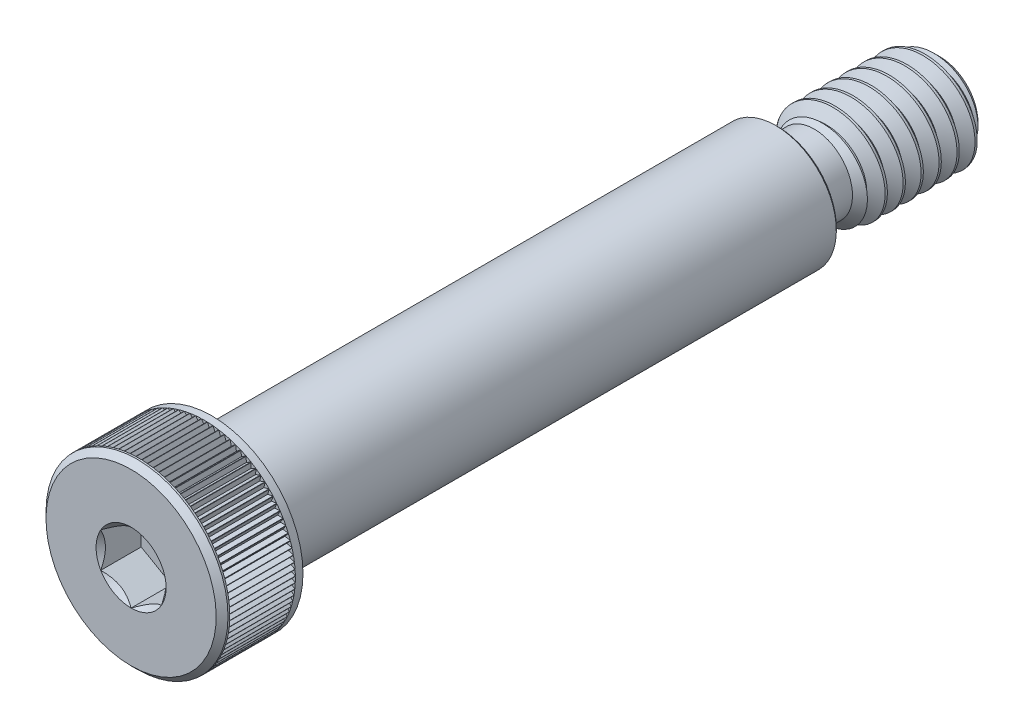
SolidWorks part; units mm, degrees
ref_plane "Front" through (0, 0, 0) normal (0, 0, 1) x (1, 0, 0)
ref_plane "Top" through (0, 0, 0) normal (0, 1, 0) x (1, 0, 0)
ref_plane "Right" through (0, 0, 0) normal (1, 0, 0) x (0, 0, -1)
sketch "Sketch1" plane through (0, 0, 0) normal (1, 0, 0) x (0, 0, -1)
  line L0 (0, 7.1437) -> (6.35, 7.1437)
  line L1 (6.35, 7.1437) -> (6.35, 4.7625)
  line L2 (6.35, 4.7625) -> (50.8, 4.7625)
  line L3 (50.8, 4.7625) -> (50.8, 3.9751)
  line L4 (50.8, 3.9751) -> (63.5, 3.9751)
  line L5 (63.5, 3.9751) -> (63.5, 0)
  line L6 (63.5, 0) -> (0, 0)
  line L7 (0, 0) -> (0, 7.1437)
  line L8 (0, 7.1437) -> (0, -7.1438) construction
  line L9 (63.5, 3.9751) -> (63.5, -3.9751) construction
  line L10 (50.8, 4.7625) -> (50.8, -4.7625) construction
  line L11 (63.5, -3.9751) -> (61.8222, -3.9751) construction
  line L12 (28.575, 0) -> (28.575, 4.7625) construction
  point P8 (61.3833, -3.9751)
  point P12 (50.8, 0)
  point P17 (10.795, 4.7625)
  point P18 (28.575, 0)
  point P19 (28.575, 4.7625)
  point P20 (46.355, 4.7625)
  point P21 (46.355, -4.7625)
  point P22 (10.795, -4.7625)
  dimension "Head Dia" = 14.2875
  dimension "Head Ht" = 6.35
  dimension "Thread Lg" = 12.7
  dimension "Thread Dia" = 7.9502
  dimension "Shoulder Dia" = 9.525
  dimension "Shoulder Lg" = 44.45
  dimension "D1" = 2.1167
  dimension "D2" = 1.6778
  dimension "D3" = 22.225
  dimension "D4" = 4.445
revolve "Revolve1" add sketch "Sketch1" angle 360 mid plane about L6
ref_plane "Plane1" through (0, 0, -63.5) normal (0, 0, 1) x (1, 0, 0)
sketch "Sketch3" plane through (0, 0, -63.5) normal (0, 0, 1) x (1, 0, 0)
  circle A0 centre (0, 0) radius 3.9751
sketch "Sketch5" plane through (0, 0, 0) normal (1, 0, 0) x (0, 0, -1)
  line L0 (50.8, 4.7625) -> (55.372, 4.7625)
  line L1 (55.372, 4.7625) -> (53.6194, 3.0099)
  line L2 (53.6194, 3.0099) -> (51.7652, 3.0099)
  line L3 (50.8, 4.7625) -> (50.8, 3.9751)
  line L5 (50.8, 3.9751) -> (63.5, 3.9751) construction
  line L6 (63.5, 0) -> (53.6194, 0) construction
  line L7 (58.5597, 0) -> (58.5597, -3.9751) construction
  arc A0 (50.8, 3.9751) -> (51.7652, 3.0099) centre (51.7652, 3.9751) ccw
  dimension "D1" = 45
  dimension "CADB" = 2.8194
  dimension "CADA" = 6.0198
revolve "Cut-Revolve1" cut sketch "Sketch5" angle 360 mid plane about L6
chamfer "Chamfer1" distance 0.9938 angle 45 1 edges at (0, 3.9751, -63.5)
chamfer "Chamfer2" distance 0.4643 angle 45 1 edges at (0, 7.1437, 0)
chamfer "Chamfer3" distance 0.2032 angle 45 1 edges at (0, 4.7625, -50.8)
sketch "Sketch10" plane through (0, 0, 0) normal (1, 0, 0) x (0, 0, -1)
  line L0 (0.4643, 0) -> (5.8857, 0) construction
  line L1 (0.4643, -7.1437) -> (0.4643, 7.1437) construction
  line L3 (0.4643, 0) -> (0, 0) construction
  line L4 (5.8857, 0) -> (6.35, 0) construction
  line L5 (6.35, -7.1438) -> (6.35, 7.1437) construction
  point P6 (3.175, 0)
  dimension "D1" = 5.4213
ref_plane "Plane2" through (0, 0, -3.175) normal (0, 0, 1) x (1, 0, 0)
sketch "Sketch11" plane through (0, 0, -3.175) normal (0, 0, 1) x (1, 0, 0)
  line L0 (0, 6.7723) -> (0, 7.1437) construction
  line L1 (0, 6.7723) -> (0.2145, 7.1437)
  line L2 (0, 6.7723) -> (-0.2145, 7.1437)
  line L3 (-0.2145, 7.1437) -> (0.2145, 7.1437)
  line L4 (0, 0) -> (-0.2145, 7.1437) construction
  line L5 (0.2145, 7.1437) -> (0, 0) construction
  circle A1 centre (0, 0) radius 7.1437 construction
  circle A2 centre (0, 0) radius 6.7723 construction
  circle A3 centre (0, 0) radius 6.6794 construction
  point P3 (0, 0.0018)
  point P8 (2.3908, 0.7309)
  dimension "D1" = 0.3715
  dimension "D2" = 3.439
extrude "Cut-Extrude5" cut sketch "Sketch11" against normal mid plane 5.1502
pattern_circular "CirPattern1" count 99 over 360 about axis through (0, 0, -63.5) along (0, 0, -1) of "Cut-Extrude5"
sketch "Sketch8" plane through (0, 0, 0) normal (0, 0, 1) x (1, 0, 0)
  line L1 (2.3813, 1.3748) -> (0, 2.7496)
  line L2 (0, 2.7496) -> (-2.3812, 1.3748)
  line L3 (-2.3812, 1.3748) -> (-2.3812, -1.3748)
  line L4 (-2.3812, -1.3748) -> (0, -2.7496)
  line L5 (0, -2.7496) -> (2.3813, -1.3748)
  line L6 (2.3813, -1.3748) -> (2.3813, 1.3748)
  circle A0 centre (0, 0) radius 2.3812 construction
  dimension "Hex" = 4.7625
extrude "Cut-Extrude2" cut sketch "Sketch8" against normal blind 3.175
sketch "Sketch9" plane through (0, 0, 0) normal (0, 0, 1) x (1, 0, 0)
  circle A0 centre (0, 0) radius 2.7496
extrude "Cut-Extrude4" cut sketch "Sketch9" against normal blind 3.175 draft 45
sketch "Front Sketch" plane through (0, 0, 0) normal (0, 0, 1) x (1, 0, 0)
  line L0 (2.3813, -1.3748) -> (2.3813, 1.3748) construction
  line L1 (-2.3812, 1.3748) -> (-2.3812, -1.3748) construction
  circle A0 centre (0, 0) radius 7.1437 construction
  point P4 (-2.3812, 0)
  point P5 (2.3813, 0)
  point P6 (7.1437, 0)
  point P9 (-7.1437, 0)
ref_plane "Contact Plane 1" through (0, 0, -6.35) normal (0, 0, -1) x (-1, 0, 0)
ref_axis "Center Axis 1" through (0, 0, -63.5) along (0, 0, 1)
curve "Helix/Spiral1" pitch 1.4111 height 14.1111 radius 3.9751 centre (0, 0, -63.5) axis (0, 0, 1) start towards (0, 1, 0)
sketch "Sketch4" plane through (0, 0, 0) normal (1, 0, 0) x (0, 0, -1)
  line L0 (63.4118, 4.1279) -> (64.8229, 4.1279) construction
  line L1 (64.8229, 4.1279) -> (64.1174, 2.9058) construction
  line L3 (64.1174, 2.9058) -> (63.4118, 4.1279) construction
  line L4 (63.4559, 4.0515) -> (64.7788, 4.0515) construction
  line L5 (63.5, 3.9751) -> (64.7347, 3.9751) construction
  line L6 (64.0292, 3.0586) -> (64.2056, 3.0586) construction
  line L7 (64.1174, 3.0586) -> (64.1174, 2.9058) construction
  line L8 (64.1174, 4.1279) -> (64.1174, 3.9751) construction
  line L9 (63.4559, 4.0515) -> (64.7788, 4.0515)
  line L10 (64.7788, 4.0515) -> (64.2056, 3.0586)
  line L11 (64.2056, 3.0586) -> (64.0292, 3.0586)
  line L12 (64.0292, 3.0586) -> (63.4559, 4.0515)
  point P14 (64.1174, 4.0515)
  point P15 (64.1174, 4.1279)
  dimension "D1" = 1.4111
  dimension "D2" = 0.1764
sweep "Cut-Sweep1" cut profiles "Sketch4" path "Helix/Spiral1" align with end faces yes
sketch "Sketch12" plane through (0, 0, 0) normal (1, 0, 0) x (0, 0, -1)
  line L1 (50.8, 4.5593) -> (50.5968, 4.7625)
  line L2 (50.5968, 4.7625) -> (6.35, 4.7625)
  line L3 (6.35, 4.7625) -> (6.35, 0)
  line L4 (6.35, -7.1438) -> (6.35, 7.1437) construction
  line L5 (6.35, 0) -> (50.8, 0)
  line L6 (50.8, 4.5593) -> (50.8, 3.9751)
  line L7 (53.6194, 3.0099) -> (51.7652, 3.0099) construction
  line L8 (53.6194, 3.0099) -> (51.7652, 3.0099)
  line L9 (53.6194, 3.0099) -> (53.6194, 0)
  line L10 (53.6194, 0) -> (50.8, 0)
  arc A0 (50.8, 3.9751) -> (51.7652, 3.0099) centre (51.7652, 3.9751) ccw construction
  arc A1 (50.8, 3.9751) -> (51.7652, 3.0099) centre (51.7652, 3.9751) ccw
revolve "Revolve2" add sketch "Sketch12" angle 360 about L5
equation "\"D3@Helix/Spiral1\" = \"Thread Lg@Sketch1\" + \"D4@Helix/Spiral1\""
equation "\"D1@Chamfer1\" = \"Thread Dia@Sketch1\" * .125"
equation "\"D1@Cut-Extrude2\"= \"Head Ht@Sketch1\" * .5"
equation "\"D1@Cut-Extrude4\" = \"D1@Cut-Extrude2\""
equation "\"D1@Chamfer2\" = \"Head Dia@Sketch1\" * .0325"
equation "\"D1@Sketch1\"=\"D4@Helix/Spiral1\"*1.5"
equation "\"D1@Sketch11\"=\"D1@Chamfer2\"*.8"
equation "\"D1@Cut-Extrude5\"=\"D1@Sketch10\"*.95"
equation "\"D1@CirPattern1\"=(360/\"D2@Sketch11\")-6"
equation "\"D3@Sketch1\"=\"Shoulder Lg@Sketch1\"/2"
equation "\"D4@Sketch1\"=\"D3@Sketch1\"*.2"
equation "\"D1@Sketch4\"=\"D4@Helix/Spiral1\""
equation "\"D2@Sketch4\"=\"D1@Sketch4\"/8"
